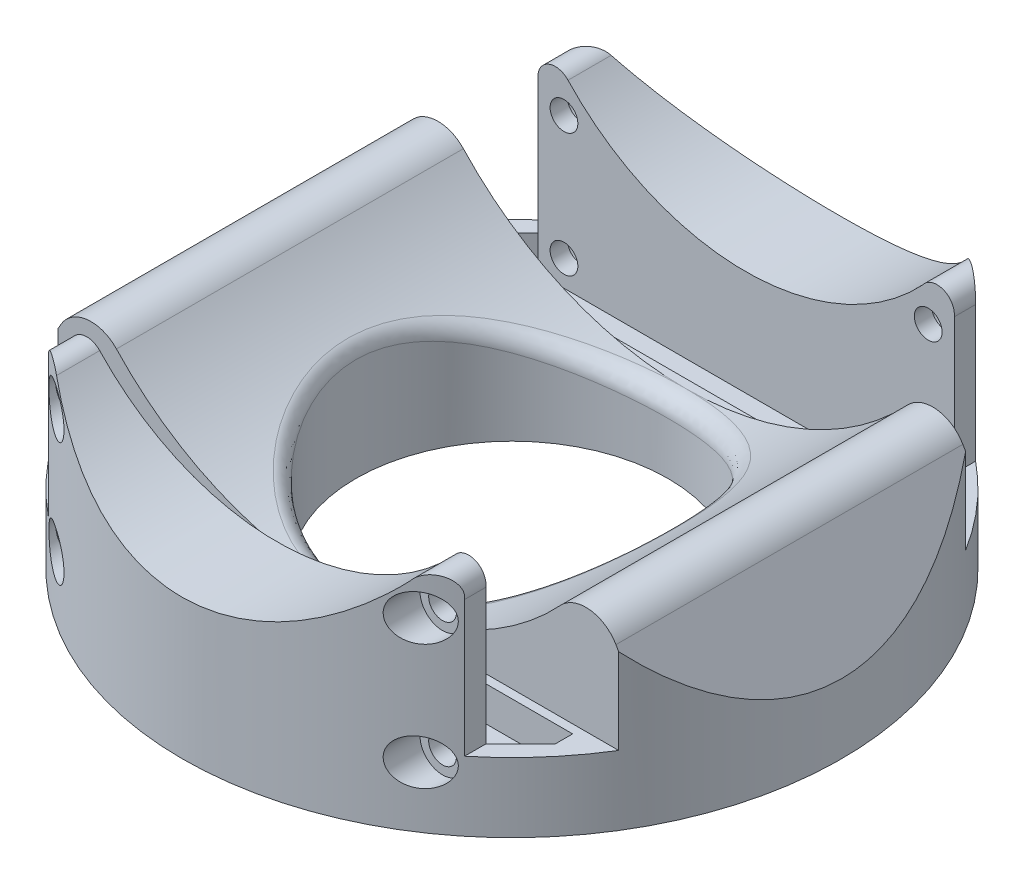
SolidWorks part; units mm, degrees
ref_plane "Front Plane" through (0, 0, 0) normal (0, 0, 1) x (1, 0, 0)
ref_plane "Top Plane" through (0, 0, 0) normal (0, 1, 0) x (1, 0, 0)
ref_plane "Right Plane" through (0, 0, 0) normal (1, 0, 0) x (0, 0, -1)
sketch "Sketch6" plane through (0, 0, 0) normal (0, 1, 0) x (1, 0, 0)
  line L0 (65, 62.5) -> (60, 67.5)
  line L1 (70, 57.5) -> (65, 62.5)
  line L2 (70, 52.5) -> (70, 57.5)
  line L3 (-70, 52.5) -> (70, 52.5)
  line L4 (-70, 57.5) -> (-70, 52.5)
  line L5 (-65, 62.5) -> (-70, 57.5)
  line L6 (-60, 67.5) -> (-65, 62.5)
  line L7 (60, 67.5) -> (-60, 67.5)
  line L8 (0, 0) -> (0, 52.5)
  line L9 (0, 0) -> (0, -52.5)
  line L10 (0, 0) -> (20.887, 0) construction
  line L11 (60, -67.5) -> (-60, -67.5)
  line L12 (-60, -67.5) -> (-65, -62.5)
  line L13 (-65, -62.5) -> (-70, -57.5)
  line L14 (-70, -57.5) -> (-70, -52.5)
  line L15 (-70, -52.5) -> (70, -52.5)
  line L16 (70, -52.5) -> (70, -57.5)
  line L17 (70, -57.5) -> (65, -62.5)
  line L18 (65, -62.5) -> (60, -67.5)
  circle A0 centre (0, 0) radius 95
  point P12 (0, 52.5)
extrude "Boss-Extrude3" add sketch "Sketch6" along normal blind 10 and the other way blind 10 contours L10 A0 L15 L16 L17 L18 L11 L12 L13 L14 | A0 L10 L3 L4 L5 L6 L7 L0 L1 L2 region at (-92.313, 0, 0)
sketch "Sketch7" plane through (0, 0, 0) normal (0, 0, 1) x (1, 0, 0)
  line L0 (-60, 0) -> (60, 0)
  line L1 (60, 0) -> (60, 49.1068)
  line L2 (-60, 49.1068) -> (-60, 0)
  line L3 (-52.5, 43.123) -> (-52.5, 7.5)
  line L4 (-52.5, 7.5) -> (52.5, 7.5)
  line L5 (52.5, 7.5) -> (52.5, 43.5339)
  arc A0 (60, 49.1068) -> (51.0068, 52.6342) centre (55.0315, 49.6675) ccw
  arc A1 (-51.3333, 52.5061) -> (51.0068, 52.6342) centre (-0.2231, 100.3364) ccw
  arc A2 (-51.3333, 52.5061) -> (-60, 49.1068) centre (-55, 49.1068) ccw
  arc A3 (-52.5, 43.123) -> (-52.5, 43.123) centre (-52.5, 43.123) ccw
  arc A4 (52.5, 43.5339) -> (52.5, 43.5339) centre (52.5, 43.5339) ccw
  arc A5 (-52.5, 43.123) -> (52.5, 43.5339) centre (-0.2231, 100.3364) ccw
  circle A6 centre (-52.5, 43.123) radius 5
  circle A7 centre (-52.5, 7.5) radius 5
  circle A8 centre (52.5, 7.5) radius 5
  circle A9 centre (52.5, 43.5339) radius 5
  point P17 (0, 0)
  dimension "D1" = 7.5
extrude "Boss-Extrude4" add sketch "Sketch7" along normal blind 30 from offset 67.5 contours A1 A2 L2 L0 L1 A0 A9 L5 A8 L4 A7 L3 A6 A5 | A9 A5 A6 L3 A7 L4 A8 L5 region at (-58.6811, 24.5534, 0) region at (0.1503, 19.1638, 0)
sketch "Sketch8" plane through (0, 0, 97.5) normal (0, 0, 1) x (1, 0, 0)
  circle A0 centre (-52.5, 7.5) radius 5
  circle A1 centre (52.5, 7.5) radius 5
extrude "Cut-Extrude2" cut sketch "Sketch8" against normal blind 30
sketch "Sketch12" plane through (0, 0, 67.5) normal (0, 0, -1) x (-1, 0, 0)
  circle A0 centre (52.5, 43.123) radius 4
  circle A1 centre (52.5, 43.123) radius 5
  circle A2 centre (52.5, 7.5) radius 5
  circle A3 centre (52.5, 7.5) radius 4
  circle A4 centre (-52.5, 7.5) radius 4
  circle A5 centre (-52.5, 7.5) radius 5
  circle A6 centre (-52.5, 43.5339) radius 5
  circle A7 centre (-52.5, 43.5339) radius 4
extrude "Boss-Extrude5" add sketch "Sketch12" against normal blind 5
sketch "Sketch13" plane through (0, 0, 72.5) normal (0, 0, 1) x (1, 0, 0)
  circle A0 centre (-52.5, 43.123) radius 6.5
  circle A1 centre (-52.5, 7.5) radius 6.5
  circle A2 centre (52.5, 43.5339) radius 6.5
  circle A3 centre (52.5, 7.5) radius 6.5
extrude "Cut-Extrude6" cut sketch "Sketch13" along normal blind 15
sketch "Sketch14" plane through (0, -10, 0) normal (0, -1, 0) x (1, 0, 0)
  line L0 (-60, 73.6546) -> (-60, 97.5)
  line L1 (-60, 97.5) -> (60, 97.5)
  line L2 (60, 97.5) -> (60, 73.6546)
  circle A0 centre (0, 0) radius 95
  circle M8 centre (0, 0) radius 95
extrude "Cut-Extrude7" cut sketch "Sketch14" against normal blind 98 contours L2 L1 L0 M8 region at (-58.7765, -10, 85.5773)
sketch "Sketch15" plane through (60, 0, 0) normal (-1, 0, 0) x (0, 0, 1)
  line L0 (97.5, 49.1068) -> (97.5, 50.2283)
  line L1 (97.5, 50.2283) -> (73.6546, 50.2283)
  line L2 (73.6546, 50.2283) -> (73.6546, 49.1068)
  line L3 (73.6546, 49.1068) -> (97.5, 49.1068)
extrude "Cut-Extrude8" cut sketch "Sketch15" against normal blind 98
ref_plane "Plane1" through (0, 0, 0) normal (0, 0, -1) x (-1, 0, 0)
mirror "Mirror1" about plane through (0, 0, 0) normal (0, 0, -1) of "Boss-Extrude4", "Cut-Extrude2", "Cut-Extrude8", "Cut-Extrude7", "Cut-Extrude6", "Boss-Extrude5"
sketch "Sketch16" plane through (0, 0, 0) normal (0, 0, 1) x (1, 0, 0)
  line L0 (0, 0) -> (0, 10)
  line L1 (0, 10) -> (95, 10)
  line L2 (0, 10) -> (-95, 10)
  line L3 (0, 10) -> (0, 185)
  line L4 (-95, 10) -> (-87.5, 97.5)
  line L5 (87.5, 97.5) -> (95, 10)
  line L6 (-95, 10) -> (-64.3602, 38.2209)
  line L7 (95, 10) -> (64.3602, 38.2209)
  line L8 (64.3602, 38.2209) -> (-64.3602, 38.2209)
  line L9 (-95, 10) -> (-72.6433, 48.7229)
  line L10 (95, 10) -> (72.6433, 48.7229)
  circle A0 centre (0, 97.5) radius 87.5
  dimension "D1" = 60
extrude "Boss-Extrude6" add sketch "Sketch16" along normal blind 50 and the other way blind 50 contours A0 L9 L6 | A0 L6 L2 | A0 L1 L7 | A0 L7 L10 region at (60.048, 18.7071, 0) region at (-60.048, 18.7071, 0) region at (77.407, 32.2227, 0) region at (-77.407, 32.2227, 0)
sketch "Sketch17" plane through (0, 10, 0) normal (0, -1, 0) x (1, 0, 0)
  line L0 (80.7775, 50) -> (95, 50)
  line L1 (95, 50) -> (95, -50)
  line L2 (95, -50) -> (80.7775, -50)
  line L3 (-80.7775, -50) -> (-95, -50)
  line L4 (-95, -50) -> (-95, 50)
  line L5 (-95, 50) -> (-80.7775, 50)
  circle A0 centre (0, 0) radius 95
  arc M1 (80.7775, 50) -> (95, 0) centre (0, 0) cw
  line M2 (95, 0) -> (95, 50)
  line M3 (95, 50) -> (80.7775, 50)
extrude "Cut-Extrude9" cut sketch "Sketch17" against normal blind 50 contours A0 L2 L1 | M3 M1 M2 | A0 L5 L4 | A0 L4 L3 region at (90.7942, 10, 37.6949) region at (90.7942, 10, -37.6949) region at (-90.7942, 10, 37.6949) region at (-90.7942, 10, -37.6949)
fillet "Fillet1" radius 10 2 edges at (-72.6433, 48.7229, 0) (72.6433, 48.7229, 0)
sketch "Sketch18" plane through (0, -10, 0) normal (0, -1, 0) x (1, 0, 0)
  line L40 (70, 57.5) -> (60, 67.5)
  line L41 (70, 52.5) -> (70, 57.5)
  line L42 (-70, 52.5) -> (70, 52.5)
  line L43 (-70, 57.5) -> (-70, 52.5)
  line L44 (60, 67.5) -> (-60, 67.5)
  line L45 (-60, 67.5) -> (-70, 57.5)
  line L46 (70, 57.5) -> (60, 67.5)
  line L47 (70, 52.5) -> (70, 57.5)
  line L48 (-70, 52.5) -> (70, 52.5)
  line L49 (-70, 57.5) -> (-70, 52.5)
  line L50 (60, 67.5) -> (-60, 67.5)
  line L51 (-60, 67.5) -> (-70, 57.5)
  line L73 (-60, -67.5) -> (60, -67.5)
  line L74 (60, -67.5) -> (70, -57.5)
  line L75 (70, -57.5) -> (70, -52.5)
  line L76 (70, -52.5) -> (-70, -52.5)
  line L77 (-70, -52.5) -> (-70, -57.5)
  line L78 (-70, -57.5) -> (-60, -67.5)
  line L79 (-60, -67.5) -> (60, -67.5)
  line L80 (60, -67.5) -> (70, -57.5)
  line L81 (70, -57.5) -> (70, -52.5)
  line L82 (70, -52.5) -> (-70, -52.5)
  line L83 (-70, -52.5) -> (-70, -57.5)
  line L84 (-70, -57.5) -> (-60, -67.5)
  dimension "D1" = 0
  dimension "D2" = 0
extrude "Boss-Extrude7" add sketch "Sketch18" against normal blind 10
sketch "Sketch19" plane through (0, -10, 0) normal (0, -1, 0) x (1, 0, 0)
  circle A0 centre (0, 0) radius 45
extrude "Cut-Extrude10" cut sketch "Sketch19" against normal blind 47
fillet "Fillet3" radius 5 1 edges at (-4.2301, 10.1023, 44.8007)
